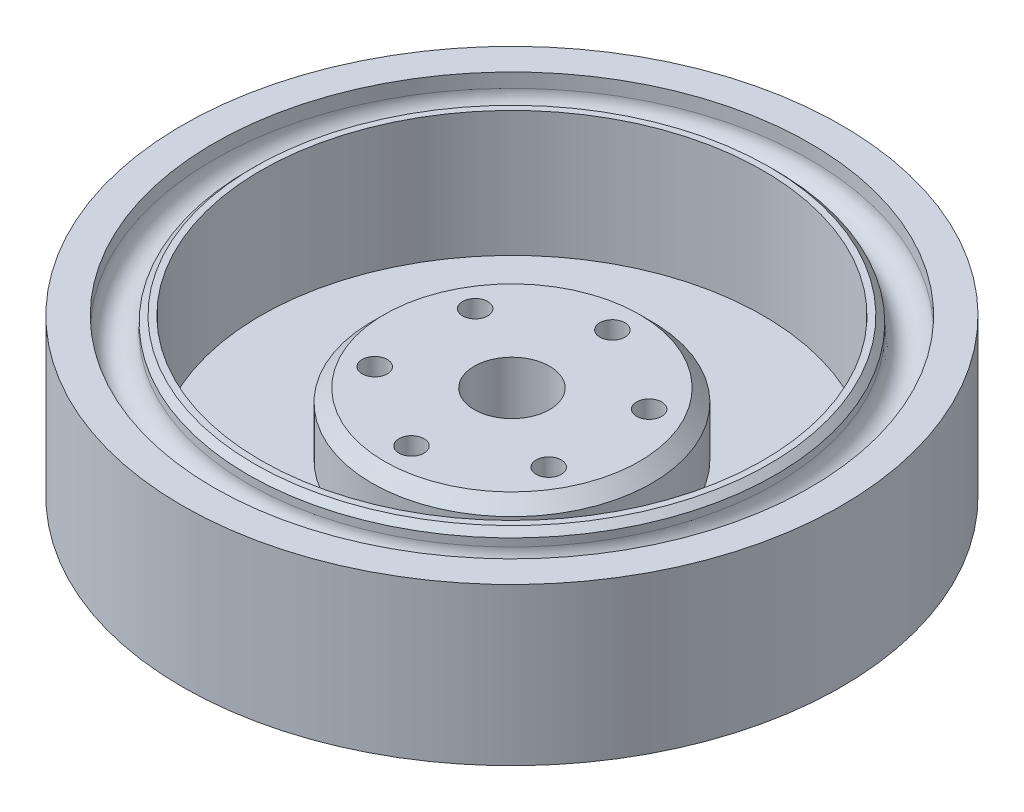
SolidWorks part; units mm, degrees
ref_plane "Plan de face" through (0, 0, 0) normal (0, 0, 1) x (1, 0, 0)
ref_plane "Plan de dessus" through (0, 0, 0) normal (0, 1, 0) x (1, 0, 0)
ref_plane "Plan de droite" through (0, 0, 0) normal (1, 0, 0) x (0, 0, -1)
sketch "Esquisse1" plane through (0, 0, 0) normal (0, 1, 0) x (1, 0, 0)
  circle A0 centre (0, 0) radius 52.5
  dimension "D1" = 105
extrude "Boss.-Extru.1" add sketch "Esquisse1" along normal blind 25
sketch "Esquisse2" plane through (0, 25, 0) normal (0, 1, 0) x (1, 0, 0)
  circle A0 centre (0, 0) radius 40
  dimension "D1" = 80
extrude "Enlèv. mat.-Extru.1" cut sketch "Esquisse2" against normal blind 20
sketch "Esquisse3" plane through (0, 5, 0) normal (0, 1, 0) x (1, 0, 0)
  circle A0 centre (0, 0) radius 22.3
  dimension "D1" = 44.6
extrude "Boss.-Extru.2" add sketch "Esquisse3" along normal blind 10
chamfer "Chanfrein1" distance 2 angle 45 1 edges at (0, 15, 22.3)
sketch "Esquisse4" plane through (0, 15, 0) normal (0, 1, 0) x (1, 0, 0)
  line L0 (0, 16) -> (0, 0) construction
  circle A0 centre (0, 16) radius 2
  circle A1 centre (13.8564, 8) radius 2
  circle A2 centre (13.8564, -8) radius 2
  circle A3 centre (0, -16) radius 2
  circle A4 centre (-13.8564, -8) radius 2
  circle A5 centre (-13.8564, 8) radius 2
  circle A6 centre (0, 0) radius 20.3 construction
  circle A7 centre (0, 0) radius 6
  dimension "D2" = 4
  dimension "D4" = 12
  dimension "D1" = 16
  dimension "D3" = 6
extrude "Enlèv. mat.-Extru.2" cut sketch "Esquisse4" against normal up to next
sketch "Esquisse5" plane through (0, 25, 0) normal (0, 1, 0) x (1, 0, 0)
  circle A0 centre (0, 0) radius 42
  circle A1 centre (0, 0) radius 47.5
  dimension "D1" = 84
  dimension "D2" = 95
extrude "Enlèv. mat.-Extru.3" cut sketch "Esquisse5" against normal blind 5
fillet "Congé2" 2 edges at (0, 20, 42) (0, 20, 47.5) type full round first side face at (0, 20, 42) second side face at (0, 20, 47.5) middle face at (0, 20, 42)
chamfer "Chanfrein2" distance 1 angle 45 1 edges at (0, 25, 42)
sketch "Esquisse6" plane through (0, 0, 0) normal (0, -1, 0) x (1, 0, 0)
  line L0 (0, 16) -> (0, 0) construction
  circle A0 centre (0, 16) radius 5
  circle A1 centre (13.8564, 8) radius 5
  circle A2 centre (13.8564, -8) radius 5
  circle A3 centre (0, -16) radius 5
  circle A4 centre (-13.8564, -8) radius 5
  circle A5 centre (-13.8564, 8) radius 5
  dimension "D1" = 10
  dimension "D2" = 16
  dimension "D3" = 6
extrude "Enlèv. mat.-Extru.4" cut sketch "Esquisse6" against normal blind 5
